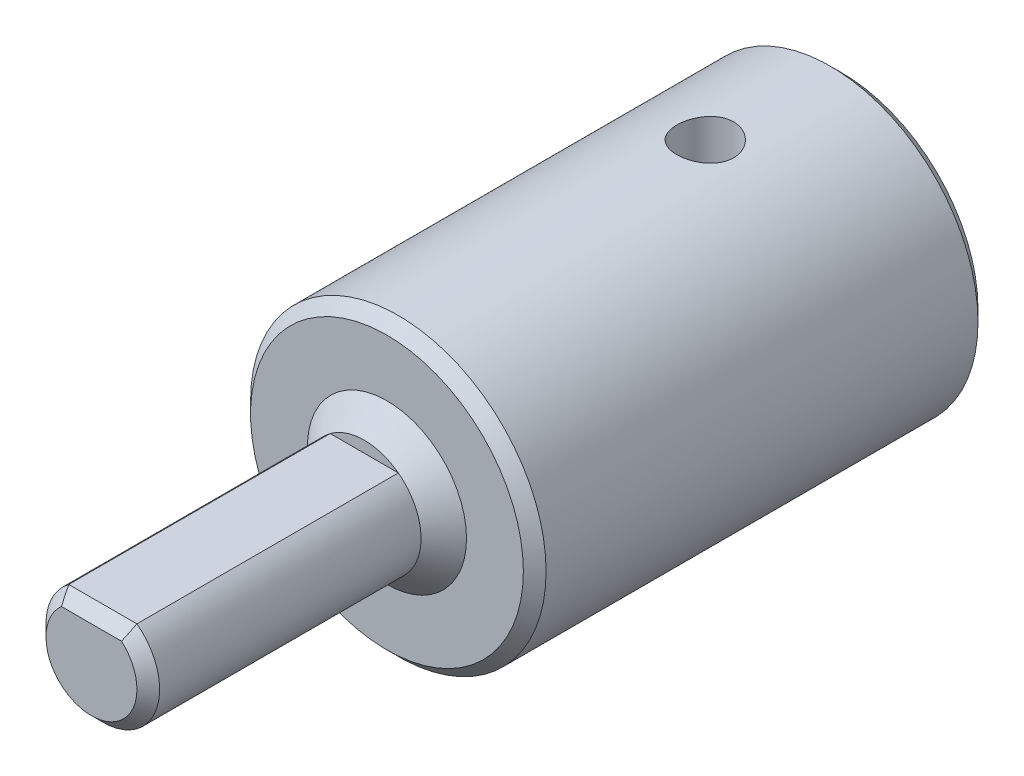
SolidWorks part; units mm, degrees
ref_plane "前视基准面" through (0, 0, 0) normal (0, 0, 1) x (1, 0, 0)
ref_plane "上视基准面" through (0, 0, 0) normal (0, 1, 0) x (1, 0, 0)
ref_plane "右视基准面" through (0, 0, 0) normal (1, 0, 0) x (0, 0, -1)
sketch "草图1" plane through (0, 0, 0) normal (0, 0, 1) x (1, 0, 0)
  circle A0 centre (0, 0) radius 6.5
  dimension "D1" = 13
extrude "凸台-拉伸1" add sketch "草图1" along normal blind 20
sketch "草图2" plane through (0, 0, 0) normal (0, 0, -1) x (-1, 0, 0)
  line L0 (-3.1225, 2.5) -> (3.1225, 2.5)
  line L1 (0, 0) -> (0, -4)
  circle A0 centre (0, 0) radius 4
  dimension "D1" = 8
  dimension "D2" = 6.5
extrude "切除-拉伸1" cut sketch "草图2" against normal blind 17 contours L0 A0 region at (0, 2.3969, 0)
sketch "草图3" plane through (0, 0, 20) normal (0, 0, 1) x (1, 0, 0)
  circle A0 centre (0, 0) radius 2.5
  dimension "D1" = 5
extrude "凸台-拉伸2" add sketch "草图3" along normal blind 13
sketch "草图4" plane through (0, 0, 33) normal (0, 0, 1) x (1, 0, 0)
  line L0 (-1.5, 2) -> (1.5, 2)
  line L1 (0, 2.5) -> (0, 0)
  circle A0 centre (0, 0) radius 2.5 construction
  circle A1 centre (0, 0) radius 2.5 construction
  circle A3 centre (0, 0) radius 2.5
  circle A4 centre (0, 0) radius 2.5
  circle M3 centre (0, 0) radius 2.5
  dimension "D1" = 0.5
  dimension "D2" = 0
extrude "切除-拉伸2" cut sketch "草图4" against normal blind 12 contours L1 L0 M3 | L1 L0 M3 region at (-0.5708, 2.2018, 33) region at (0.5708, 2.2018, 33)
chamfer "倒角1" distance 1 angle 45 1 edges at (2.5, 0, 20)
sketch "草图5" plane through (0, 0, 0) normal (0, 0, -1) x (-1, 0, 0)
  line L3 (3.1702, 2.6) -> (-3.1702, 2.6)
  line L4 (3.1702, 2.6) -> (-3.1702, 2.6)
  arc A2 (-3.1702, 2.6) -> (3.1702, 2.6) centre (0, 0) ccw
  arc A3 (-3.1702, 2.6) -> (3.1702, 2.6) centre (0, 0) ccw
  dimension "D1" = 0.1
extrude "切除-拉伸3" cut sketch "草图5" against normal up to surface (17 mm away) up to face at (0, -0.75, 17)
chamfer "倒角2" distance 0.5 angle 45 2 edges at (0, 2, 33) (0, -2.5, 33)
chamfer "倒角3" distance 0.5 angle 45 4 edges at (0, 2.6, 0) (0, -4.1, 0) (6.5, 0, 0) (6.5, 0, 20)
sketch "草图6" plane through (0, 0, 0) normal (0, 1, 0) x (1, 0, 0)
  line L0 (6, 0) -> (-6, 0) construction
  circle A0 centre (0, -6) radius 1.25
  dimension "D1" = 2.5
  dimension "D2" = 6
extrude "切除-拉伸4" cut sketch "草图6" along normal blind 10
